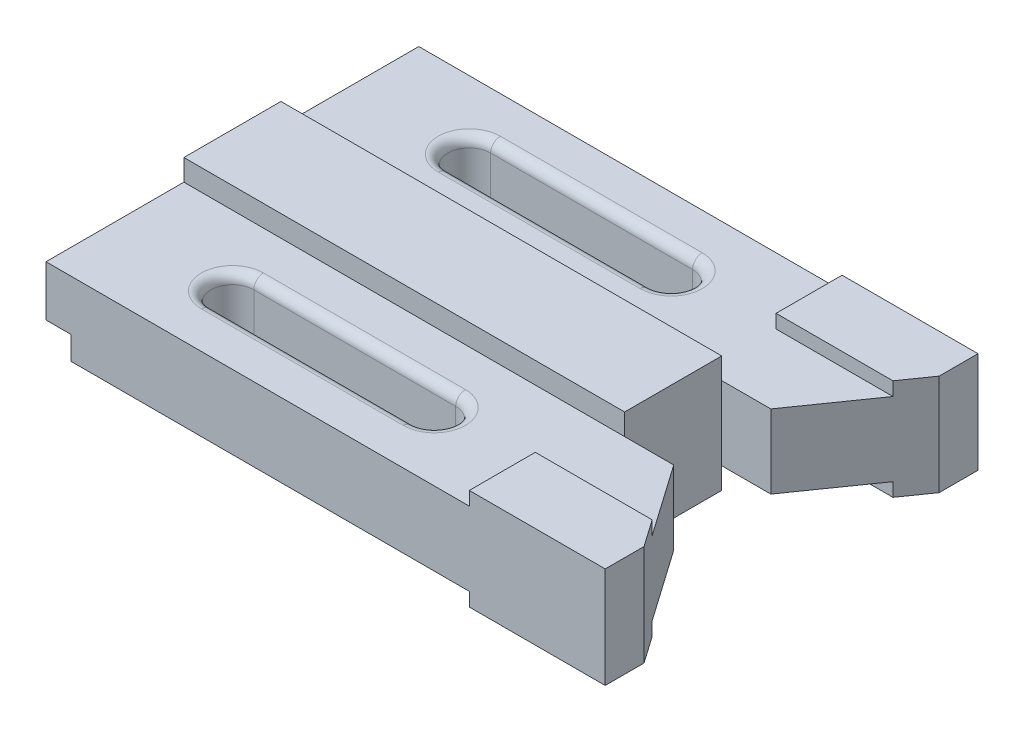
SolidWorks part; units mm, degrees
material "Alliage 1060"
ref_plane "Plan de face" through (0, 0, 0) normal (0, 0, 1) x (1, 0, 0)
ref_plane "Plan de dessus" through (0, 0, 0) normal (0, 1, 0) x (1, 0, 0)
ref_plane "Plan de droite" through (0, 0, 0) normal (1, 0, 0) x (0, 0, -1)
sketch "Esquisse1" plane through (0, 0, 0) normal (0, 1, 0) x (1, 0, 0)
  line L0 (0, 0) -> (-143.5103, 0) construction
  line L1 (0, -12.5) -> (0, 12.5)
  line L2 (-113.5, 12.5) -> (12.6447, 12.5)
  line L3 (12.6447, 12.5) -> (30.5, 38)
  line L4 (30.5, 38) -> (30.5, 48)
  line L5 (30.5, 48) -> (-113.5, 48)
  line L6 (-113.5, 48) -> (-113.5, -48)
  line L7 (-83, -30.5) -> (-31, -30.5) construction
  line L8 (-83, 30.5) -> (-31, 30.5) construction
  line L9 (-83, 36) -> (-31, 36)
  line L10 (-83, 25) -> (-31, 25)
  line L11 (25.5985, 31) -> (-4.5, 31)
  line L12 (-4.5, 31) -> (-4.5, 48)
  line L13 (-83, -36) -> (-31, -36)
  line L14 (-83, -25) -> (-31, -25)
  line L15 (-4.5, -31) -> (-4.5, -48)
  line L16 (25.5985, -31) -> (-4.5, -31)
  line L17 (30.5, -48) -> (-113.5, -48)
  line L18 (30.5, -38) -> (30.5, -48)
  line L19 (12.6447, -12.5) -> (30.5, -38)
  line L20 (-113.5, -12.5) -> (12.6447, -12.5)
  arc A0 (-83, 36) -> (-83, 25) centre (-83, 30.5) ccw
  arc A1 (-31, 25) -> (-31, 36) centre (-31, 30.5) ccw
  arc A2 (-83, -36) -> (-83, -25) centre (-83, -30.5) cw
  arc A3 (-31, -25) -> (-31, -36) centre (-31, -30.5) cw
  point P12 (-57, 30.5)
  point P24 (-57, -30.5)
  point P33 (-113.5, 0)
  dimension "D3" = 5.5
  dimension "D1" = 96
  dimension "D2" = 17.5
  dimension "D4" = 52
  dimension "D5" = 30.5
  dimension "D6" = 10
  dimension "D7" = 35.5
  dimension "D8" = 17
  dimension "D9" = 35
  dimension "D10" = 144
  dimension "D11" = 55
  dimension "D12" = 30.5
extrude "Boss.-Extru.1" add sketch "Esquisse1" along normal mid plane 30 contours L6 L20 L1 L2 region at (-56.75, 0, 0)
extrude "Boss.-Extru.2" add sketch "Esquisse1<3>" along normal offset from surface 5.5 and the other way offset from surface 5.5 contours L20 L6 L17 L15 L16 L19 L14 A3 L13 A2 | L11 L12 L5 L6 L2 L3 A1 L10 A0 L9 region at (6.3224, 0, 13.9356) region at (-56.75, 0, -13.9356) up to face at (-56.75, 15, 0) other way up to face at (-56.75, -15, 0)
sketch "Esquisse1<3>" plane through (0, 0, 0) normal (0, 1, 0) x (1, 0, 0) same geometry as "Esquisse1"
extrude "Boss.-Extru.3" add sketch "Esquisse1<4>" along normal mid plane 26 contours L12 L11 L3 L4 L5 | L19 L16 L15 L17 L18 region at (12.529, 0, 39.6831) region at (12.529, 0, -39.6831)
sketch "Esquisse1<4>" plane through (0, 0, 0) normal (0, 1, 0) x (1, 0, 0) same geometry as "Esquisse1"
sketch "Esquisse2" plane through (0, 0, 0) normal (0, 0, 1) x (1, 0, 0)
  line L0 (-113.5, 9.5) -> (-113.5, -9.5) construction
  line L1 (-113.5, -3.5) -> (-107, -3.5)
  line L2 (-113.5, -3.5) -> (-113.5, -15)
  line L3 (-113.5, -15) -> (-107, -15)
  line L4 (-107, -3.5) -> (-107, -15)
  line L5 (-113.5, -15) -> (0, -15) construction
  dimension "D1" = 11.5
  dimension "D2" = 6.5
extrude "Enlèv. mat.-Extru.1" cut sketch "Esquisse2" against normal through all and the other way through all
fillet "Congé1" radius 2.5 16 edges at (-25.5, -9.5, 30.5) (-57, -9.5, 25) (-88.5, -9.5, 30.5) (-57, -9.5, -36) (-88.5, -9.5, -30.5) (-57, -9.5, -25) (-57, 9.5, 36) (-25.5, 9.5, 30.5) (-57, 9.5, 25) (-57, 9.5, -36) (-25.5, 9.5, -30.5) (-57, 9.5, -25) (-57, -9.5, 36) (-25.5, -9.5, -30.5) (-88.5, 9.5, 30.5) (-88.5, 9.5, -30.5)
equation "\"A\"= 144"
equation "\"B\"= 52"
equation "\"C\"= 55deg"
equation "\"D4@Esquisse1\"=\"B\""
equation "\"D10@Esquisse1\"=\"A\""
equation "\"D11@Esquisse1\"=\"C\""
